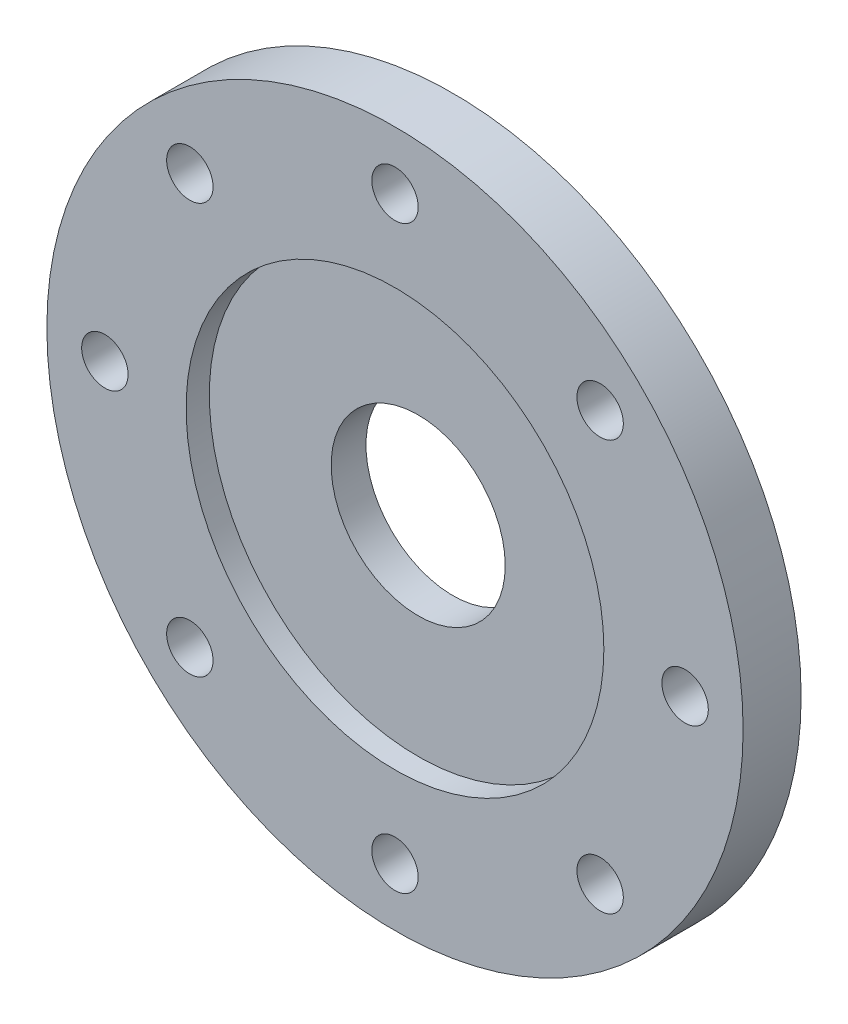
SolidWorks part; units mm, degrees
material "6061-T6 (SS)"
ref_plane "Front Plane" through (0, 0, 0) normal (0, 0, 1) x (1, 0, 0)
ref_plane "Top Plane" through (0, 0, 0) normal (0, 1, 0) x (1, 0, 0)
ref_plane "Right Plane" through (0, 0, 0) normal (1, 0, 0) x (0, 0, -1)
sketch "Sketch1" plane through (0, 0, 0) normal (0, 0, 1) x (1, 0, 0)
  circle A0 centre (0, 0) radius 15.875 construction
  circle A1 centre (0, 15.875) radius 1.27
  circle A2 centre (11.2253, 11.2253) radius 1.27
  circle A3 centre (15.875, 0) radius 1.27
  circle A4 centre (0, 0) radius 19.05
  circle A5 centre (0, 0) radius 4.7625
  circle A6 centre (11.2253, -11.2253) radius 1.27
  circle A7 centre (0, -15.875) radius 1.27
  circle A8 centre (-11.2253, -11.2253) radius 1.27
  circle A9 centre (-15.875, 0) radius 1.27
  circle A10 centre (-11.2253, 11.2253) radius 1.27
  dimension "D2" = 2.54
  dimension "D3" = 8
  dimension "D5" = 38.1
  dimension "D6" = 9.525
  dimension "D1" = 31.75
extrude "Boss-Extrude1" add sketch "Sketch1" along normal blind 3.175
sketch "Sketch2" plane through (0, 0, 3.175) normal (0, 0, 1) x (1, 0, 0)
  circle A0 centre (0, 0) radius 11.43
  dimension "D1" = 22.86
extrude "Cut-Extrude1" cut sketch "Sketch2" against normal blind 1.27
